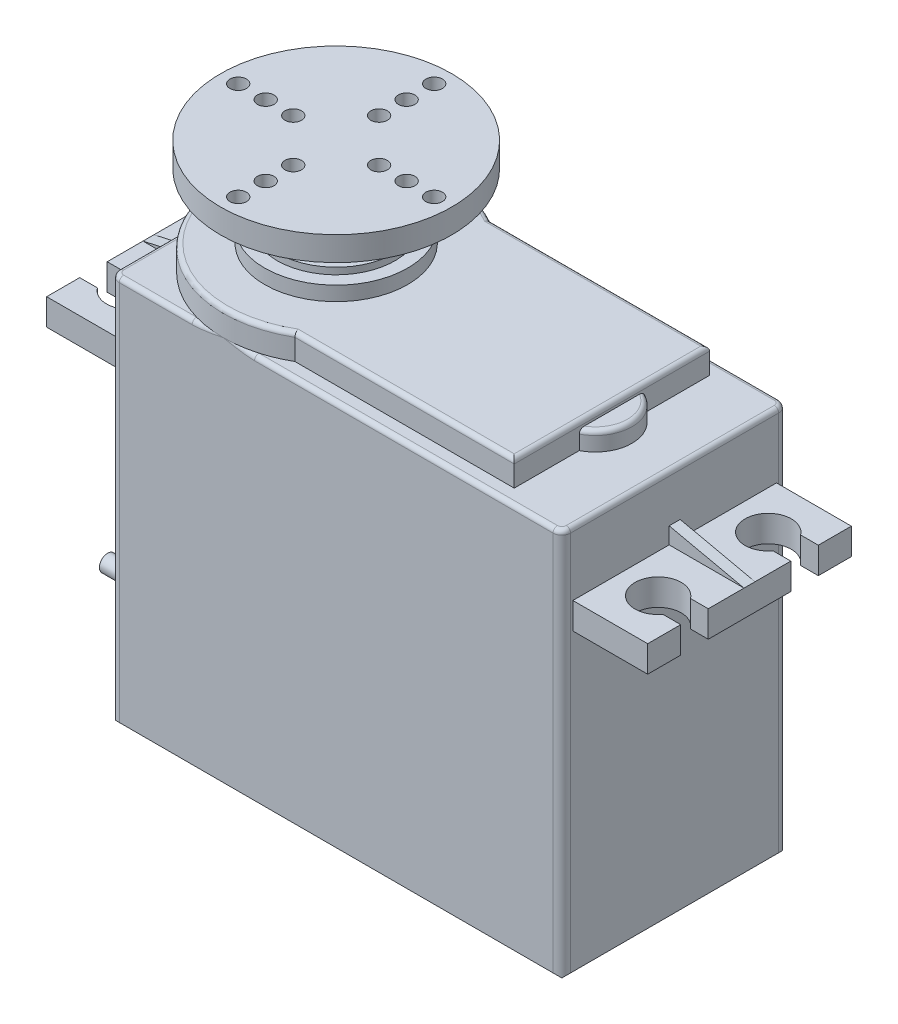
SolidWorks part; units mm, degrees
ref_plane "Plan de face" through (0, 0, 0) normal (0, 0, 1) x (1, 0, 0)
ref_plane "Plan de dessus" through (0, 0, 0) normal (0, 1, 0) x (1, 0, 0)
ref_plane "Plan de droite" through (0, 0, 0) normal (1, 0, 0) x (0, 0, -1)
sketch "Esquisse1" plane through (0, 0, 0) normal (0, 1, 0) x (1, 0, 0)
  line L1 (0, 0) -> (41, 0)
  line L2 (0, 0) -> (0, 20.5)
  line L3 (0, 20.5) -> (41, 20.5)
  line L4 (41, 0) -> (41, 20.5)
  dimension "D1" = 41
  dimension "D2" = 20.5
extrude "Boss.-Extru.1" add sketch "Esquisse1" along normal blind 37
sketch "Esquisse2" plane through (0, 37, 0) normal (0, 1, 0) x (1, 0, 0)
  line L0 (0, 20.5) -> (0, 0) construction
  line L1 (41, 0) -> (41, 20.5) construction
  line L2 (15.378, 1.375) -> (35.3, 1.375)
  line L3 (35.3, 13.2174) -> (35.3, 19.125)
  line L4 (15.378, 19.125) -> (35.3, 19.125)
  line L6 (0, 10.25) -> (40.5565, 10.25) construction
  line L7 (35.3, 1.375) -> (35.3, 7.2826)
  line L8 (18.9815, 4.8813) -> (35.3, 19.125) construction
  line L9 (18.9815, 15.6187) -> (35.3, 1.375) construction
  line L10 (0, 0) -> (41, 0) construction
  circle A0 centre (10.25, 10.25) radius 10.25
  arc A1 (35.3, 7.2826) -> (35.3, 13.2174) centre (33.8, 10.25) ccw
  point P0 (25.1322, 10.25)
  dimension "D5" = 6.65
  dimension "D1" = 10.25
  dimension "D2" = 5.7
  dimension "D3" = 17.75
  dimension "D4" = 10.25
  dimension "D6" = 1.5
extrude "Boss.-Extru.2" add sketch "Esquisse2" along normal blind 2.3 contours L7 A1 L3 L4 A0 L2 | A0 region at (27.3254, 37, -10.25) region at (10.25, 37, -10.25)
sketch "Esquisse3" plane through (0, 39.3, 0) normal (0, 1, 0) x (1, 0, 0)
  circle A0 centre (10.25, 10.25) radius 6.5
extrude "Boss.-Extru.3" add sketch "Esquisse3" along normal blind 1.3
sketch "Esquisse4" plane through (0, 40.6, 0) normal (0, 1, 0) x (1, 0, 0)
  circle A0 centre (10.25, 10.25) radius 5.35
  dimension "D1" = 10.7
extrude "Boss.-Extru.4" add sketch "Esquisse4" along normal blind 0.6
sketch "Esquisse5" plane through (0, 39.3, 0) normal (0, 1, 0) x (1, 0, 0)
  line L0 (35.3, 13.2174) -> (35.3, 7.2826)
  arc A0 (35.3, 7.2826) -> (35.3, 13.2174) centre (33.8, 10.25) ccw
extrude "Enlèv. mat.-Extru.1" cut sketch "Esquisse5" against normal blind 0.6
sketch "Esquisse6" plane through (0, 41.2, 0) normal (0, 1, 0) x (1, 0, 0)
  circle A0 centre (10.25, 10.25) radius 3
extrude "Boss.-Extru.5" add sketch "Esquisse6" along normal blind 4
chamfer "Chanfrein1" distance 2 angle 45 4 edges at (20.5, 0, 0) (41, 0, -10.25) (20.5, 0, -20.5) (0, 0, -10.25)
fillet "Congé1" radius 0.8 4 edges at (0, 19.5, 0) (0, 19.5, -20.5) (41, 19.5, 0) (41, 19.5, -20.5)
sketch "Esquisse7" plane through (0, 0, 0) normal (-1, 0, 0) x (0, 0, 1)
  line L0 (-19.7, 37) -> (-10.25, 37) construction
  line L1 (-19.5, 28.8) -> (-1, 28.8)
  line L2 (-19.5, 28.8) -> (-19.5, 31.2)
  line L3 (-19.5, 31.2) -> (-1, 31.2)
  line L4 (-1, 28.8) -> (-1, 31.2)
  line L5 (-19.5, 28.8) -> (-1, 31.2) construction
  line L6 (-19.5, 31.2) -> (-1, 28.8) construction
  point P0 (-10.25, 30)
  dimension "D1" = 18.5
  dimension "D3" = 2.4
  dimension "D4" = 5.8
extrude "Boss.-Extru.6" add sketch "Esquisse7" along normal blind 6.8
sketch "Esquisse8" plane through (0, 31.2, 0) normal (0, 1, 0) x (1, 0, 0)
  line L0 (10.25, 10.25) -> (-8.9274, 10.25) construction
  line L2 (-6.8, 1) -> (-6.8, 19.5) construction
  line L3 (-6.8, 16.5) -> (-5.1875, 16.5)
  line L4 (-5.1875, 14) -> (-6.8, 14)
  line L5 (-5.1875, 6.5) -> (-6.8, 6.5)
  line L6 (-6.8, 4) -> (-5.1875, 4)
  arc A0 (-5.1875, 14) -> (-5.1875, 16.5) centre (-3.5, 15.25) ccw
  arc A1 (-5.1875, 6.5) -> (-5.1875, 4) centre (-3.5, 5.25) cw
  line M3 (-6.8, 19.5) -> (-6.8, 1)
  dimension "D1" = 4.2
  dimension "D2" = 5
  dimension "D3" = 3.3
  dimension "D4" = 2.5
  dimension "D5" = 1.25
extrude "Enlèv. mat.-Extru.2" cut sketch "Esquisse8" against normal through all and the other way through all contours L4 A0 L3 M3 | A1 L5 L6 M3 region at (-4.0093, 31.2, -5.25) region at (-4.0093, 31.2, -15.25)
sketch "Esquisse9" plane through (0, 31.2, 0) normal (0, 1, 0) x (1, 0, 0)
  line L1 (-6.8, 6.5) -> (-6.8, 14) construction
  line L2 (0.0294, 10.75) -> (-6.8, 10.75)
  line L3 (0.0294, 10.75) -> (0.0294, 9.75)
  line L4 (0.0294, 9.75) -> (-6.8, 9.75)
  line L5 (-6.8, 10.75) -> (-6.8, 9.75)
  line L6 (0.0294, 10.75) -> (-6.8, 9.75) construction
  line L7 (0.0294, 9.75) -> (-6.8, 10.75) construction
  line L8 (-6.8, 14) -> (-6.8, 6.5) construction
  point P0 (-3.3853, 10.25)
  point P10 (-6.8, 10.25)
  dimension "D1" = 1
  dimension "D2" = 0
extrude "Boss.-Extru.7" add sketch "Esquisse9" along normal blind 1.5
ref_plane "Plan1" through (20.5, 0, 0) normal (1, 0, 0) x (0, 0, -1)
mirror "Symétrie1" about plane through (20.5, 0, 0) normal (1, 0, 0) of "Boss.-Extru.6", "Boss.-Extru.7", "Enlèv. mat.-Extru.2"
chamfer "Chanfrein2" distance 1.5 distance2 6.8 1 edges at (-6.8, 32.7, -10.25) first distance on face at (-6.8, 30.975, -10.25)
chamfer "Chanfrein3" distance 6.8 distance2 1.5 1 edges at (47.8, 32.7, -10.25) first distance on face at (44.4, 32.7, -10.25)
fillet "Congé2" radius 0.4 16 edges at (37.125, 38.7, -10.25) (35.3, 39.3, -10.25) (25.339, 39.3, -19.125) (0, 39.3, -10.25) (25.339, 39.3, -1.375) (5.525, 37, 0) (0.2343, 37, -0.2343) (0, 37, -5.525) (0, 37, -14.975) (0.2343, 37, -20.2657) (5.525, 37, -20.5) (25.225, 37, -20.5) (40.7657, 37, -20.2657) (41, 37, -10.25) (40.7657, 37, -0.2343) (25.225, 37, 0)
sketch "Esquisse10" plane through (0, 0, 0) normal (-1, 0, 0) x (0, 0, 1)
  line L0 (-2, 0) -> (-18.5, 0) construction
  line L1 (-13.75, 3.2) -> (-6.75, 3.2)
  line L2 (-13.75, 3.2) -> (-13.75, 7.4)
  line L3 (-13.75, 7.4) -> (-6.75, 7.4)
  line L4 (-6.75, 3.2) -> (-6.75, 7.4)
  line L5 (-13.75, 3.2) -> (-6.75, 7.4) construction
  line L6 (-13.75, 7.4) -> (-6.75, 3.2) construction
  line L7 (-19.7, 2) -> (-0.8, 2) construction
  point P0 (-10.25, 5.3)
  dimension "D1" = 7
  dimension "D2" = 4.2
  dimension "D3" = 3.2
extrude "Boss.-Extru.8" add sketch "Esquisse10" along normal blind 1
sketch "Esquisse11" plane through (-1, 0, 0) normal (-1, 0, 0) x (0, 0, 1)
  line L0 (-13.4, 7.05) -> (-13.4, 3.55)
  line L5 (-13.4, 3.55) -> (-7.1, 3.55)
  line L6 (-7.1, 7.05) -> (-7.1, 3.55)
  line L7 (-13.4, 7.05) -> (-7.1, 7.05)
extrude "Boss.-Extru.9" add sketch "Esquisse11" along normal blind 4 draft 5
sketch "Esquisse12" plane through (-5, 0, 0) normal (-1, 0, 0) x (0, 0, 1)
  line L1 (-13.05, 3.9) -> (-7.45, 3.9) construction
  line L2 (-13.05, 6.7) -> (-13.05, 3.9) construction
  circle A0 centre (-10.25, 5.3) radius 0.75
  circle A1 centre (-8.74, 5.3) radius 0.75
  circle A2 centre (-11.76, 5.3) radius 0.75
  dimension "D1" = 1.5
  dimension "D2" = 1.51
  dimension "D3" = 1.51
  dimension "D4" = 1.4
  dimension "D5" = 2.8
extrude "Boss.-Extru.11" add sketch "Esquisse12" along normal blind 4
sketch "Esquisse13" plane through (0, 45.2, 0) normal (0, 1, 0) x (1, 0, 0)
  circle A0 centre (10.25, 10.25) radius 10.5
extrude "Boss.-Extru.12" add sketch "Esquisse13" along normal blind 2.2
sketch "Esquisse14" plane through (0, 47.4, 0) normal (0, 1, 0) x (1, 0, 0)
  circle A0 centre (10.25, 14.15) radius 0.75
  circle A1 centre (10.25, 10.25) radius 10.5 construction
  circle A2 centre (10.25, 16.65) radius 0.75
  circle A3 centre (10.25, 19.15) radius 0.75
  circle A4 centre (14.15, 10.25) radius 0.75
  circle A5 centre (16.65, 10.25) radius 0.75
  circle A6 centre (19.15, 10.25) radius 0.75
  circle A7 centre (10.25, 6.35) radius 0.75
  circle A8 centre (10.25, 3.85) radius 0.75
  circle A9 centre (10.25, 1.35) radius 0.75
  circle A10 centre (6.35, 10.25) radius 0.75
  circle A11 centre (3.85, 10.25) radius 0.75
  circle A12 centre (1.35, 10.25) radius 0.75
  point P4 (0, 0)
  dimension "D1" = 1.5
  dimension "D2" = 3.9
  dimension "D3" = 3
  dimension "D4" = 4
extrude "Enlèv. mat.-Extru.3" cut sketch "Esquisse14" against normal up to next
